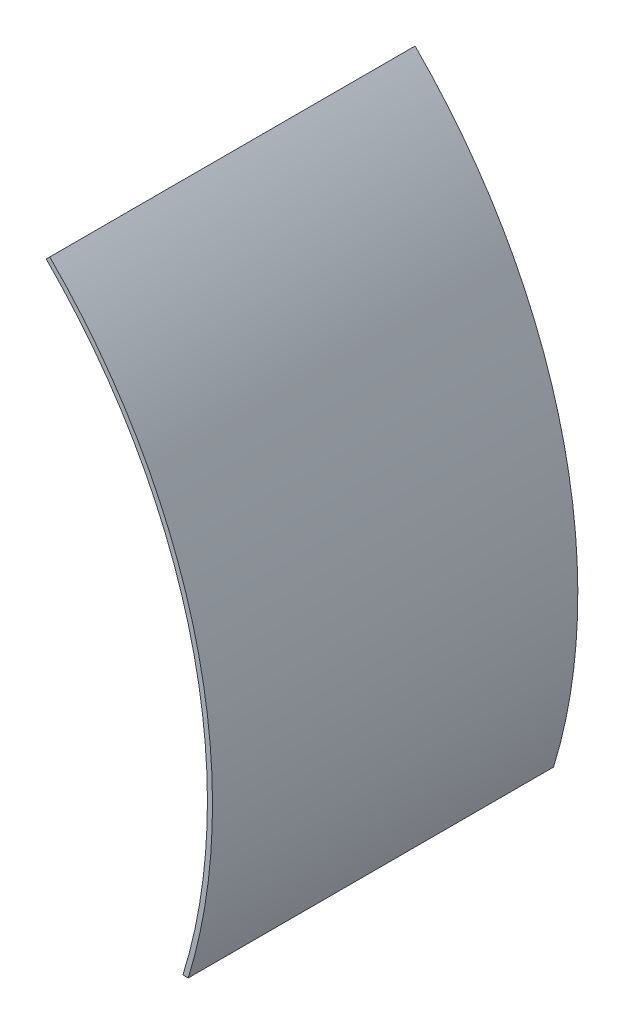
SolidWorks part; units mm, degrees
material "PE High Density"
ref_plane "Front Plane" through (0, 0, 0) normal (0, 0, 1) x (1, 0, 0)
ref_plane "Top Plane" through (0, 0, 0) normal (0, 1, 0) x (1, 0, 0)
ref_plane "Right Plane" through (0, 0, 0) normal (1, 0, 0) x (0, 0, -1)
sketch "Sketch1" plane through (0, 0, 0) normal (0, 0, 1) x (1, 0, 0)
  line L0 (0, 0) -> (172.2438, 0) construction
  line L1 (0, 0) -> (121.7947, 121.7947) construction
  line L2 (172.2438, 0) -> (173.8312, 0) construction
  line L3 (121.7947, 121.7947) -> (122.9173, 122.9173)
  line L4 (172.2438, 0) -> (172.2438, -50.8) construction
  line L5 (164.5821, -50.8) -> (172.2438, -50.8) construction
  line L6 (166.2428, -50.8) -> (164.5821, -50.8)
  arc A0 (172.2438, 0) -> (121.7947, 121.7947) centre (0, 0) ccw
  arc A1 (173.8312, 0) -> (122.9173, 122.9173) centre (0, 0) ccw
  arc A2 (172.2438, 0) -> (164.5821, -50.8) centre (0, 0) cw
  arc A3 (173.8312, 0) -> (166.2428, -50.8) centre (0, 0) cw
  dimension "D2" = 45
  dimension "D3" = 1.5875
  dimension "D1" = 172.2438
  dimension "D4" = 50.8
extrude "Boss-Extrude1" add sketch "Sketch1" along normal blind 114.3
